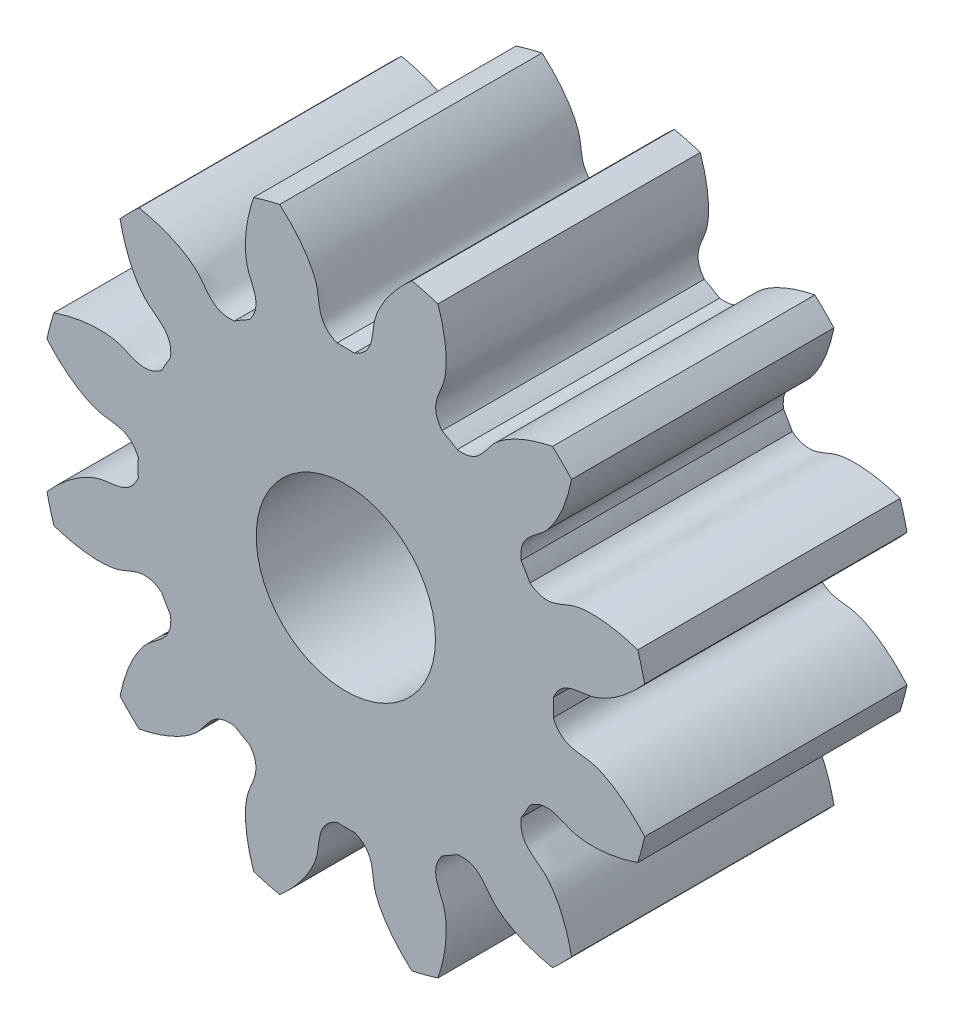
SolidWorks part; units mm, degrees
ref_plane "前视基准面" through (0, 0, 0) normal (0, 0, 1) x (1, 0, 0)
ref_plane "上视基准面" through (0, 0, 0) normal (0, 1, 0) x (1, 0, 0)
ref_plane "右视基准面" through (0, 0, 0) normal (1, 0, 0) x (0, 0, -1)
other "Configuration Table"
sketch "草图1" plane through (0, 0, 0) normal (0, 0, 1) x (1, 0, 0)
  circle A0 centre (0, 0) radius 3.5
extrude "凸台-拉伸1" add sketch "草图1" along normal blind 3
ref_axis "基准轴1" through (0, 0, 3) along (0, 0, -1)
sketch "草图2" plane through (0, 0, 0) normal (0, 0, 1) x (1, 0, 0)
  line L0 (0, 0) -> (0, 3.5) construction
  circle A0 centre (0, 0) radius 3.5 construction
  arc A1 (0.1004, 2.3729) -> (-0.1004, 2.3729) centre (0, 0) ccw
  arc A2 (1.7488, 3.9475) -> (-1.7488, 3.9475) centre (0, 0) ccw
  spline S0 degree 3 poles (0.1004, 2.3729) (0.3404, 2.4747) (0.2872, 2.6724) (0.3381, 2.8447) (0.3413, 2.855) (0.3451, 2.8662) (0.3495, 2.8784) (0.3546, 2.8915) (0.3603, 2.9056) (0.3668, 2.9206) (0.374, 2.9366) (0.3821, 2.9533) (0.3909, 2.971) (0.4007, 2.9894) (0.4114, 3.0086) (0.423, 3.0286) (0.4356, 3.0493) (0.4492, 3.0707) (0.4639, 3.0928) (0.4796, 3.1155) (0.4965, 3.1388) (0.5145, 3.1626) (0.5337, 3.187) (0.554, 3.2119) (0.5756, 3.2372) (0.5985, 3.2629) (0.6226, 3.289) (0.648, 3.3154) (0.6748, 3.342) (0.7028, 3.369) (0.7323, 3.3961) (0.7631, 3.4234) (0.7954, 3.4507) (0.829, 3.4782) (0.8641, 3.5057) (0.9006, 3.5331) (0.9385, 3.5604) (0.978, 3.5877) (1.0189, 3.6147) (1.0613, 3.6416) (1.1052, 3.6681) (1.1506, 3.6944) (1.1975, 3.7203) (1.2459, 3.7457) (1.2958, 3.7707) (1.3472, 3.7952) (1.4001, 3.8191) (1.4546, 3.8424) (1.5105, 3.865) (1.5679, 3.8869) (1.6472, 3.9154) (1.7078, 3.9351) (1.7488, 3.9475) knots 0 0 0 0 0.218015 0.222044 0.226546 0.231522 0.236972 0.242897 0.249295 0.256167 0.263513 0.271332 0.279626 0.288394 0.297636 0.307351 0.317541 0.328204 0.339341 0.350953 0.363038 0.375597 0.38863 0.402137 0.416118 0.430573 0.445502 0.460904 0.476781 0.493132 0.509956 0.527255 0.545027 0.563273 0.581994 0.601188 0.620856 0.640998 0.661614 0.682704 0.704268 0.726305 0.748817 0.771803 0.795262 0.819196 0.843603 0.868484 0.89384 0.919669 0.945972 1 1 1 1
  spline S1 degree 3 poles (-0.1004, 2.3729) (-0.3404, 2.4747) (-0.2872, 2.6724) (-0.3381, 2.8447) (-0.3413, 2.855) (-0.3451, 2.8662) (-0.3495, 2.8784) (-0.3546, 2.8915) (-0.3603, 2.9056) (-0.3668, 2.9206) (-0.374, 2.9366) (-0.3821, 2.9533) (-0.3909, 2.971) (-0.4007, 2.9894) (-0.4114, 3.0086) (-0.423, 3.0286) (-0.4356, 3.0493) (-0.4492, 3.0707) (-0.4639, 3.0928) (-0.4796, 3.1155) (-0.4965, 3.1388) (-0.5145, 3.1626) (-0.5337, 3.187) (-0.554, 3.2119) (-0.5756, 3.2372) (-0.5985, 3.2629) (-0.6226, 3.289) (-0.648, 3.3154) (-0.6748, 3.342) (-0.7028, 3.369) (-0.7323, 3.3961) (-0.7631, 3.4234) (-0.7954, 3.4507) (-0.829, 3.4782) (-0.8641, 3.5057) (-0.9006, 3.5331) (-0.9385, 3.5604) (-0.978, 3.5877) (-1.0189, 3.6147) (-1.0613, 3.6416) (-1.1052, 3.6681) (-1.1506, 3.6944) (-1.1975, 3.7203) (-1.2459, 3.7457) (-1.2958, 3.7707) (-1.3472, 3.7952) (-1.4001, 3.8191) (-1.4546, 3.8424) (-1.5105, 3.865) (-1.5679, 3.8869) (-1.6472, 3.9154) (-1.7078, 3.9351) (-1.7488, 3.9475) knots 0 0 0 0 0.218015 0.222044 0.226546 0.231522 0.236972 0.242897 0.249295 0.256167 0.263513 0.271332 0.279626 0.288394 0.297636 0.307351 0.317541 0.328204 0.339341 0.350953 0.363038 0.375597 0.38863 0.402137 0.416118 0.430573 0.445502 0.460904 0.476781 0.493132 0.509956 0.527255 0.545027 0.563273 0.581994 0.601188 0.620856 0.640998 0.661614 0.682704 0.704268 0.726305 0.748817 0.771803 0.795262 0.819196 0.843603 0.868484 0.89384 0.919669 0.945972 1 1 1 1
extrude "切除-拉伸1" cut sketch "草图2" along normal through all
pattern_circular "阵列(圆周)1" count 12 over 360 about axis through (0, 0, 3) along (0, 0, -1) of "切除-拉伸1"
sketch "草图3" plane through (0, 0, 0) normal (0, 0, 1) x (1, 0, 0)
  circle A0 centre (0, 0) radius 3 construction
  dimension "Dn" = 6
sketch "草图5" plane through (0, 0, 3) normal (0, 0, 1) x (1, 0, 0)
  circle A0 centre (0, 0) radius 1.025
  dimension "D1" = 2.05
extrude "切除-拉伸2" cut sketch "草图5" against normal up to next
